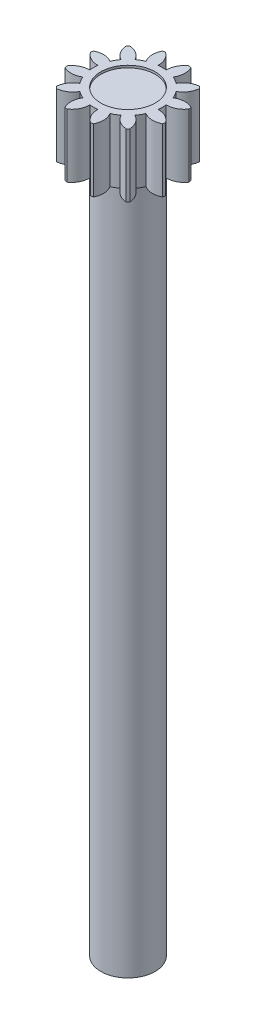
SolidWorks part; units mm, degrees
ref_plane "Front Plane" through (0, 0, 0) normal (0, 0, 1) x (1, 0, 0)
ref_plane "Top Plane" through (0, 0, 0) normal (0, 1, 0) x (1, 0, 0)
ref_plane "Right Plane" through (0, 0, 0) normal (1, 0, 0) x (0, 0, -1)
sketch "Sketch1" plane through (0, 0, 0) normal (0, 1, 0) x (1, 0, 0)
  arc A0 (-4.0574, 3.8598) -> (-3.0423, 2.2752) centre (-2.1405, 3.9703) ccw
  arc A1 (-3.0423, 2.2752) -> (-3.4916, 1.4971) centre (0, 0) ccw
  arc A2 (-3.4916, 1.4971) -> (-5.3713, 1.5839) centre (-4.5086, -0.1314) ccw
  arc A3 (-5.3713, 1.5839) -> (-5.4437, 1.314) centre (0, 0) ccw
  arc A4 (-5.4437, 1.314) -> (-3.7723, 0.4492) centre (-3.8389, 2.3681) ccw
  arc A5 (-3.7723, 0.4492) -> (-3.7723, -0.4492) centre (0, 0) ccw
  arc A6 (-3.7723, -0.4492) -> (-5.4437, -1.314) centre (-3.8389, -2.3681) ccw
  arc A7 (-5.4437, -1.314) -> (-5.3713, -1.5839) centre (0, 0) ccw
  arc A8 (-5.3713, -1.5839) -> (-3.4916, -1.4971) centre (-4.5086, 0.1314) ccw
  arc A9 (-3.4916, -1.4971) -> (-3.0423, -2.2752) centre (0, 0) ccw
  arc A10 (-3.0423, -2.2752) -> (-4.0574, -3.8598) centre (-2.1405, -3.9703) ccw
  arc A11 (-4.0574, -3.8598) -> (-3.8598, -4.0574) centre (0, 0) ccw
  arc A12 (-3.8598, -4.0574) -> (-2.2752, -3.0423) centre (-3.9703, -2.1405) ccw
  arc A13 (-2.2752, -3.0423) -> (-1.4971, -3.4916) centre (0, 0) ccw
  arc A14 (-1.4971, -3.4916) -> (-1.5839, -5.3713) centre (0.1314, -4.5086) ccw
  arc A15 (-1.5839, -5.3713) -> (-1.314, -5.4437) centre (0, 0) ccw
  arc A16 (-1.314, -5.4437) -> (-0.4492, -3.7723) centre (-2.3681, -3.8389) ccw
  arc A17 (-0.4492, -3.7723) -> (0.4492, -3.7723) centre (0, 0) ccw
  arc A18 (0.4492, -3.7723) -> (1.314, -5.4437) centre (2.3681, -3.8389) ccw
  arc A19 (1.314, -5.4437) -> (1.5839, -5.3713) centre (0, 0) ccw
  arc A20 (1.5839, -5.3713) -> (1.4971, -3.4916) centre (-0.1314, -4.5086) ccw
  arc A21 (1.4971, -3.4916) -> (2.2752, -3.0423) centre (0, 0) ccw
  arc A22 (2.2752, -3.0423) -> (3.8598, -4.0574) centre (3.9703, -2.1405) ccw
  arc A23 (3.8598, -4.0574) -> (4.0574, -3.8598) centre (0, 0) ccw
  arc A24 (4.0574, -3.8598) -> (3.0423, -2.2752) centre (2.1405, -3.9703) ccw
  arc A25 (3.0423, -2.2752) -> (3.4916, -1.4971) centre (0, 0) ccw
  arc A26 (3.4916, -1.4971) -> (5.3713, -1.5839) centre (4.5086, 0.1314) ccw
  arc A27 (5.3713, -1.5839) -> (5.4437, -1.314) centre (0, 0) ccw
  arc A28 (5.4437, -1.314) -> (3.7723, -0.4492) centre (3.8389, -2.3681) ccw
  arc A29 (3.7723, -0.4492) -> (3.7723, 0.4492) centre (0, 0) ccw
  arc A30 (3.7723, 0.4492) -> (5.4437, 1.314) centre (3.8389, 2.3681) ccw
  arc A31 (5.4437, 1.314) -> (5.3713, 1.5839) centre (0, 0) ccw
  arc A32 (5.3713, 1.5839) -> (3.4916, 1.4971) centre (4.5086, -0.1314) ccw
  arc A33 (3.4916, 1.4971) -> (3.0423, 2.2752) centre (0, 0) ccw
  arc A34 (3.0423, 2.2752) -> (4.0574, 3.8598) centre (2.1405, 3.9703) ccw
  arc A35 (4.0574, 3.8598) -> (3.8598, 4.0574) centre (0, 0) ccw
  arc A36 (3.8598, 4.0574) -> (2.2752, 3.0423) centre (3.9703, 2.1405) ccw
  arc A37 (2.2752, 3.0423) -> (1.4971, 3.4916) centre (0, 0) ccw
  arc A38 (1.4971, 3.4916) -> (1.5839, 5.3713) centre (-0.1314, 4.5086) ccw
  arc A39 (1.5839, 5.3713) -> (1.314, 5.4437) centre (0, 0) ccw
  arc A40 (1.314, 5.4437) -> (0.4492, 3.7723) centre (2.3681, 3.8389) ccw
  arc A41 (0.4492, 3.7723) -> (-0.4492, 3.7723) centre (0, 0) ccw
  arc A42 (-0.4492, 3.7723) -> (-1.314, 5.4437) centre (-2.3681, 3.8389) ccw
  arc A43 (-1.314, 5.4437) -> (-1.5839, 5.3713) centre (0, 0) ccw
  arc A44 (-1.5839, 5.3713) -> (-1.4971, 3.4916) centre (0.1314, 4.5086) ccw
  arc A45 (-1.4971, 3.4916) -> (-2.2752, 3.0423) centre (0, 0) ccw
  arc A46 (-2.2752, 3.0423) -> (-3.8598, 4.0574) centre (-3.9703, 2.1405) ccw
  arc A47 (-3.8598, 4.0574) -> (-4.0574, 3.8598) centre (0, 0) ccw
extrude "Boss-Extrude1" add sketch "Sketch1" along normal blind 7
sketch "Sketch2" plane through (0, 7, 0) normal (0, 1, 0) x (1, 0, 0)
  circle A0 centre (0, 0) radius 3
  dimension "D1" = 6
extrude "Cut-Extrude1" cut sketch "Sketch2" against normal blind 7
extrude "Boss-Extrude2" add sketch "Sketch2<2>" against normal blind 82.81 from offset 0.25 offset against normal yes
sketch "Sketch2<2>" plane through (0, 7, 0) normal (0, 1, 0) x (1, 0, 0) same geometry as "Sketch2"
sketch "Sketch3" plane through (0, 7, 0) normal (0, 1, 0) x (1, 0, 0)
  circle A0 centre (0, 0) radius 5.6
sketch "Sketch4" plane through (0, -76.06, 0) normal (0, -1, 0) x (1, 0, 0)
  point P0 (0, 0)
